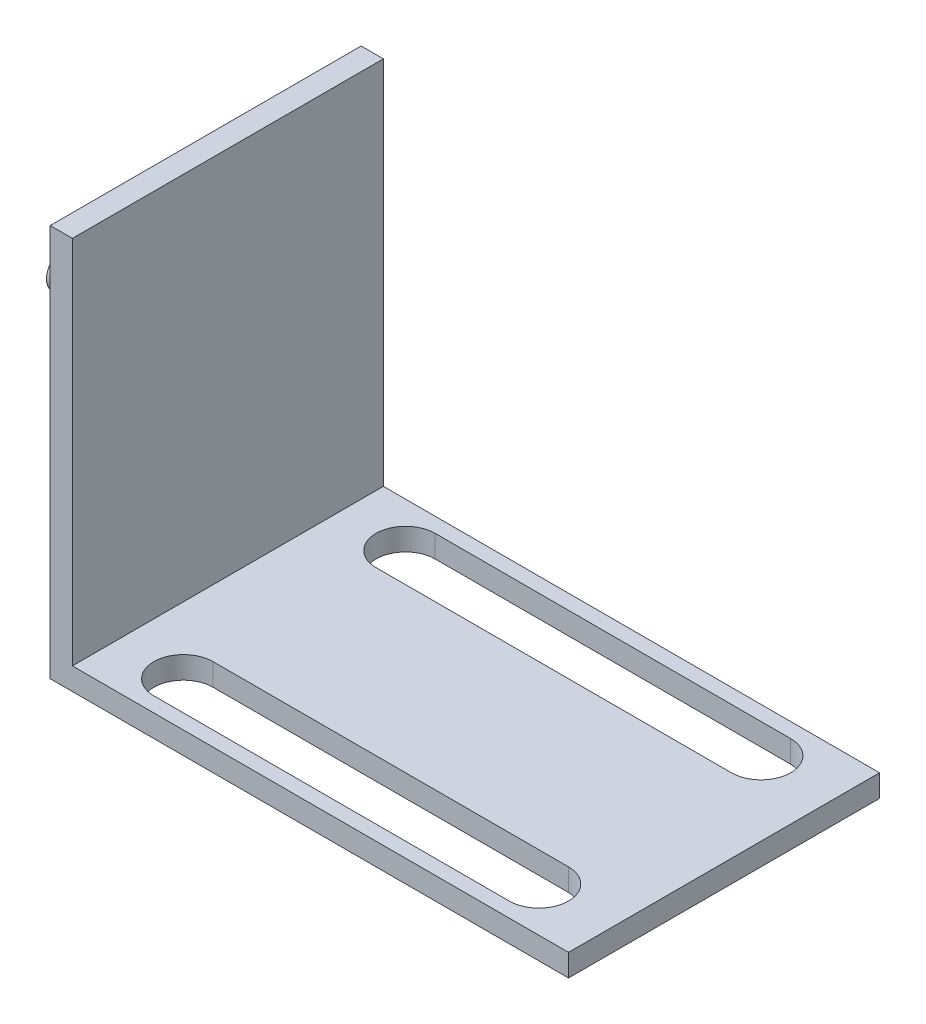
SolidWorks part; units mm, degrees
ref_plane "前视基准面" through (0, 0, 0) normal (0, 0, 1) x (1, 0, 0)
ref_plane "上视基准面" through (0, 0, 0) normal (0, 1, 0) x (1, 0, 0)
ref_plane "右视基准面" through (0, 0, 0) normal (1, 0, 0) x (0, 0, -1)
sketch "草图1" plane through (0, 0, 0) normal (0, 0, 1) x (1, 0, 0)
  line L0 (0, 53) -> (0, 0)
  line L1 (0, 0) -> (70, 0)
  line L2 (70, 0) -> (70, 3)
  line L3 (70, 3) -> (3, 3)
  line L4 (3, 3) -> (3, 53)
  line L5 (3, 53) -> (0, 53)
  dimension "D1" = 3
  dimension "D2" = 3
  dimension "D3" = 50
  dimension "D4" = 70
extrude "凸台-拉伸1" add sketch "草图1" along normal blind 21 and the other way blind 21
sketch "草图2" plane through (0, 3, 0) normal (0, 1, 0) x (1, 0, 0)
  line L0 (12, -15) -> (60, -15) construction
  line L1 (12, -11) -> (60, -11)
  line L2 (12, -19) -> (60, -19)
  line L3 (0, 0) -> (70, 0) construction
  line L4 (70, 21) -> (70, -21) construction
  line L5 (12, 15) -> (60, 15) construction
  line L6 (12, 11) -> (60, 11)
  line L7 (12, 19) -> (60, 19)
  arc A0 (12, -11) -> (12, -19) centre (12, -15) ccw
  arc A1 (60, -19) -> (60, -11) centre (60, -15) ccw
  arc A2 (12, 11) -> (12, 19) centre (12, 15) cw
  arc A3 (60, 19) -> (60, 11) centre (60, 15) cw
  point P2 (36, -15)
  point P14 (36, 15)
  dimension "D1" = 4
  dimension "D2" = 30
  dimension "D3" = 10
  dimension "D4" = 12
extrude "切除-拉伸1" cut sketch "草图2" against normal up to next
sketch "草图3" plane through (0, 0, 0) normal (-1, 0, 0) x (0, 0, 1)
  line L2 (-21, 7) -> (21, 7) construction
  line L3 (-21, 7) -> (-21, 49) construction
  line L4 (-21, 49) -> (21, 49) construction
  line L5 (21, 7) -> (21, 49) construction
  line L6 (-21, 7) -> (21, 49) construction
  line L7 (-21, 49) -> (21, 7) construction
  circle A0 centre (0, 28) radius 2.5
  point P0 (0, 28)
  dimension "D4" = 5
  dimension "D1" = 42
  dimension "D2" = 42
  dimension "D3" = 7
extrude "凸台-拉伸2" add sketch "草图3" along normal blind 19
